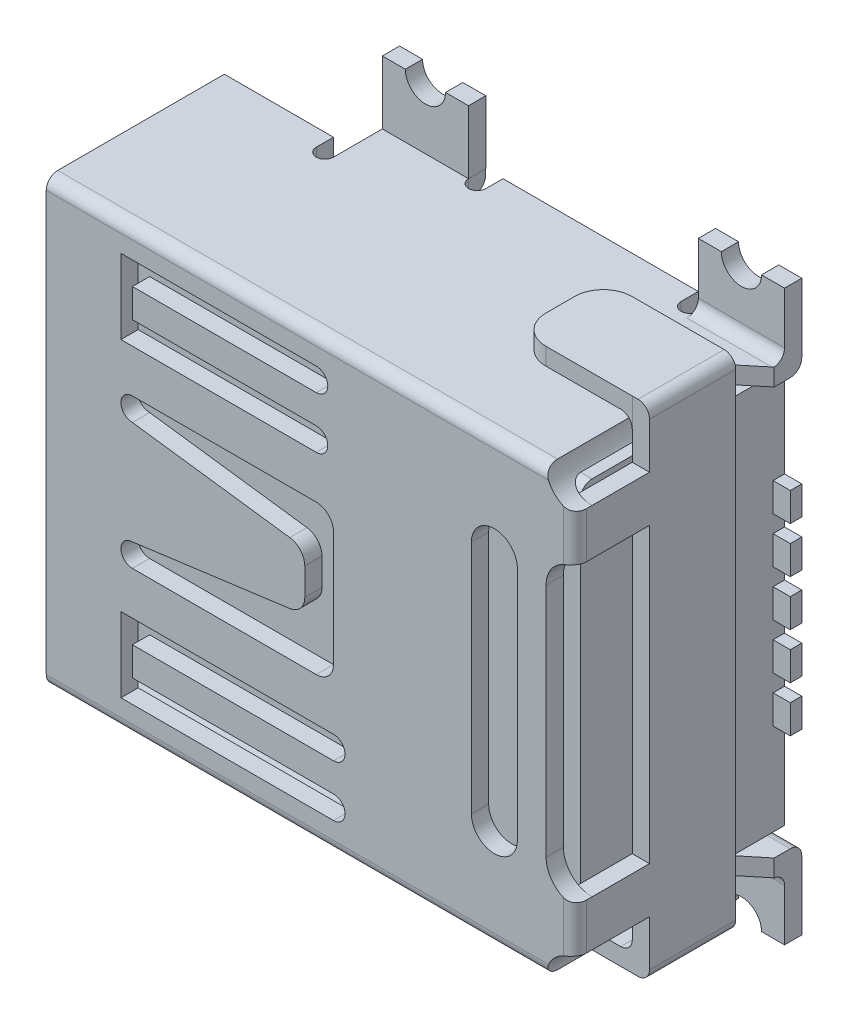
SolidWorks part; units mm, degrees
ref_plane "Front Plane" through (0, 0, 0) normal (0, 0, 1) x (1, 0, 0)
ref_plane "Top Plane" through (0, 0, 0) normal (0, 1, 0) x (1, 0, 0)
ref_plane "Right Plane" through (0, 0, 0) normal (1, 0, 0) x (0, 0, -1)
sketch "Sketch1" plane through (0, 0, 0) normal (0, 0, 1) x (1, 0, 0)
  line L0 (0, 0) -> (8.7, 0)
  line L1 (0, 7.7) -> (8.7, 7.7)
  line L2 (9.2, 7.2) -> (9.2, 6.4)
  line L3 (0, 7.7) -> (0, 0)
  line L4 (9.2, 0.5) -> (9.2, 1.3)
  line L5 (8.7, 5.9) -> (8.7, 1.8)
  line L6 (8.2, 1.8) -> (8.2, 5.9)
  line L7 (7.4, 5.9) -> (7.4, 1.8)
  line L9 (5, 4.85) -> (5, 2.85)
  line L10 (4.7, 5.15) -> (1.5, 5.15)
  line L11 (4.5, 4.0873) -> (4.5, 3.6127)
  line L12 (1.5, 4.75) -> (4.2396, 4.3847)
  line L13 (4.7, 2.55) -> (1.5, 2.55)
  line L14 (1.5, 2.95) -> (4.2396, 3.3153)
  line L15 (1.3, 5.9) -> (4.7, 5.9)
  line L16 (5, 1.8) -> (1.3, 1.8)
  line L17 (1.3, 5.9) -> (1.3, 7.2)
  line L18 (1.3, 1.8) -> (1.3, 0.5)
  line L19 (1.3, 7.2) -> (4.7, 7.2)
  line L20 (1.3, 0.5) -> (5, 0.5)
  line L21 (4.7, 6.8) -> (1.5, 6.8)
  line L22 (1.5, 6.8) -> (1.5, 6.3)
  line L23 (1.5, 6.3) -> (4.7, 6.3)
  line L24 (5, 1.4) -> (1.5, 1.4)
  line L25 (1.5, 1.4) -> (1.5, 0.9)
  line L26 (1.5, 0.9) -> (5, 0.9)
  arc A0 (8.7, 7.7) -> (9.2, 7.2) centre (9.2, 7.7) ccw
  arc A1 (8.7, 0) -> (9.2, 0.5) centre (9.2, 0) cw
  arc A2 (9.2, 6.4) -> (8.7, 5.9) centre (9.2, 5.9) ccw
  arc A3 (9.2, 1.3) -> (8.7, 1.8) centre (9.2, 1.8) cw
  arc A4 (8.2, 5.9) -> (7.4, 5.9) centre (7.8, 5.9) ccw
  arc A5 (7.4, 1.8) -> (8.2, 1.8) centre (7.8, 1.8) ccw
  arc A6 (1.5, 5.15) -> (1.5, 4.75) centre (1.5, 4.95) ccw
  arc A7 (4.7, 5.15) -> (5, 4.85) centre (4.7, 4.85) cw
  arc A8 (4.2396, 4.3847) -> (4.5, 4.0873) centre (4.2, 4.0873) cw
  arc A9 (1.5, 2.55) -> (1.5, 2.95) centre (1.5, 2.75) cw
  arc A10 (4.5, 3.6127) -> (4.2396, 3.3153) centre (4.2, 3.6127) cw
  arc A11 (5, 2.85) -> (4.7, 2.55) centre (4.7, 2.85) cw
  arc A12 (4.7, 7.2) -> (4.7, 6.8) centre (4.7, 7) cw
  arc A13 (4.7, 5.9) -> (4.7, 6.3) centre (4.7, 6.1) ccw
  arc A14 (5, 1.8) -> (5, 1.4) centre (5, 1.6) cw
  arc A15 (5, 0.5) -> (5, 0.9) centre (5, 0.7) ccw
  point P32 (5, 5.15)
  point P35 (4.5, 4.35)
  point P43 (5, 2.55)
  dimension "D1" = 9.2
  dimension "D2" = 7.7
extrude "Extrude1" add sketch "Sketch1" along normal blind 3.95
fillet "Fillet1" radius 0.2 1 edges at (4.35, 7.7, 3.95)
fillet "Fillet2" radius 0.2 1 edges at (4.35, 0, 3.95)
sketch "Sketch2" plane through (0, 0, 0) normal (-1, 0, 0) x (0, 0, 1)
  line L0 (0, 7.4) -> (3.65, 7.4)
  line L1 (0, 7.7) -> (0, 0) construction
  line L3 (3.65, 7.4) -> (3.65, 0.3)
  line L5 (3.65, 0.3) -> (0, 0.3)
  line L6 (0, 0.3) -> (0, 7.4)
extrude "Cut-Extrude1" cut sketch "Sketch2" against normal blind 9.2
fillet "Fillet5" radius 0.2 1 edges at (4.4, 7.4, 3.65)
fillet "Fillet9" radius 0.2 1 edges at (4.4, 0.3, 3.65)
sketch "Sketch4" plane through (0, 0, 0) normal (0, -1, 0) x (1, 0, 0)
  line L1 (0, 0) -> (8.7, 0) construction
  line L3 (2.2, 0.3) -> (2.2, 0)
  line L4 (3.7, 0.3) -> (3.7, 0)
  line L5 (2.2, 0.3) -> (3.7, 0.3)
  line L6 (3.7, 0) -> (2.2, 0)
extrude "Extrude3" add sketch "Sketch4" along normal blind 1.1
fillet "Fillet10" radius 0.2 1 edges at (2.95, 0, 0.3)
sketch "Sketch5" plane through (0, 0, 0) normal (0, -1, 0) x (1, 0, 0)
  line L0 (0, 0) -> (0, 0.85)
  line L1 (0, 3.75) -> (0, 0) construction
  line L3 (0, 0.85) -> (1.9, 0.85)
  line L4 (1.9, 0.85) -> (1.9, 1.35)
  line L5 (2.2, 0) -> (2.2, 1.35)
  line L6 (0, 0) -> (2.2, 0)
  arc A0 (1.9, 1.35) -> (2.2, 1.35) centre (2.05, 1.35) cw
extrude "Cut-Extrude2" cut sketch "Sketch5" against normal blind 0.3
sketch "Sketch6" plane through (0, 7.7, 0) normal (0, 1, 0) x (-1, 0, 0)
  line L0 (-2.2, 0.3) -> (-2.2, 0)
  line L3 (-8.7, 0) -> (0, 0) construction
  line L4 (-2.2, 0) -> (-3.7, 0)
  line L5 (-2.2, 0.3) -> (-3.7, 0.3)
  line L6 (-3.7, 0) -> (-3.7, 0.3)
extrude "Extrude4" add sketch "Sketch6" along normal blind 1.1
sketch "Sketch8" plane through (0, 7.7, 0) normal (0, 1, 0) x (-1, 0, 0)
  line L0 (0, 0) -> (0, 0.875)
  line L1 (0, 3.75) -> (0, 0) construction
  line L2 (0, 0.875) -> (-1.9, 0.875)
  line L3 (-2.2, 0.3) -> (-2.2, 1.15)
  line L4 (-1.9, 0.875) -> (-1.9, 1.15)
  line L5 (-2.2, 0.3) -> (-2.2, 0)
  line L6 (-2.2, 0) -> (0, 0)
  arc A0 (-1.9, 1.15) -> (-2.2, 1.15) centre (-2.05, 1.15) ccw
extrude "Cut-Extrude4" cut sketch "Sketch8" against normal blind 0.3
sketch "Sketch9" plane through (0, 0, 0) normal (0, -1, 0) x (1, 0, 0)
  line L0 (3.7, 0) -> (3.7, 0.5)
  line L1 (4, 0.5) -> (4, 0)
  line L2 (3.7, 0) -> (8.7, 0) construction
  line L3 (4, 0) -> (3.7, 0)
  arc A0 (3.7, 0.5) -> (4, 0.5) centre (3.85, 0.5) cw
extrude "Cut-Extrude5" cut sketch "Sketch9" against normal blind 0.3
fillet "Fillet11" radius 0.2 1 edges at (2.95, 0.3, 0)
sketch "Sketch10" plane through (0, 7.7, 0) normal (0, 1, 0) x (-1, 0, 0)
  line L0 (-3.6968, 0) -> (-3.7, 0.3)
  line L1 (-4, 0.2968) -> (-4, 0)
  line L2 (-8.7, 0) -> (-3.7, 0) construction
  line L3 (-4, 0) -> (-3.6968, 0)
  arc A0 (-3.7, 0.3) -> (-4, 0.2968) centre (-3.85, 0.2984) ccw
extrude "Cut-Extrude6" cut sketch "Sketch10" against normal blind 0.3
fillet "Fillet12" radius 0.2 1 edges at (2.9484, 7.4, 0)
sketch "Sketch11" plane through (9.2, 0, 0) normal (1, 0, 0) x (0, 0, -1)
  line L0 (-3.65, 7.2) -> (-2.65, 7.2)
  line L1 (-3.65, 6.4) -> (-2.65, 6.4)
  line L2 (-3.65, 7.2) -> (-3.65, 6.4)
  line L3 (-2.65, 7.2) -> (-2.65, 6.4)
extrude "Extrude5" add sketch "Sketch11" against normal blind 0.3
fillet "Fillet13" radius 0.2 1 edges at (9.2, 6.8, 3.95)
sketch "Sketch12" plane through (9.2, 0, 0) normal (1, 0, 0) x (0, 0, -1)
  line L0 (-3.65, 1.3) -> (-2.65, 1.3)
  line L1 (-3.65, 0.5) -> (-3.65, 1.3) construction
  line L2 (-3.65, 0.5) -> (-2.65, 0.5)
  line L3 (-3.65, 1.3) -> (-3.65, 0.5)
  line L4 (-2.65, 0.5) -> (-2.65, 1.3)
extrude "Extrude6" add sketch "Sketch12" against normal blind 0.3
fillet "Fillet14" radius 0.2 1 edges at (9.2, 0.9, 3.95)
sketch "Sketch13" plane through (0, 0, 2.65) normal (0, 0, -1) x (-1, 0, 0)
  line L0 (-9.2, 6.4) -> (-9.2, 1.3)
  line L1 (-8.9, 6.4) -> (-8.9, 0.5)
  line L2 (-8.9, 0.5) -> (-9.2, 0.5)
  line L3 (-9.2, 0.5) -> (-9.2, 1.3)
  line L4 (-8.9, 7.2) -> (-9.2, 7.2)
  line L5 (-9.2, 7.2) -> (-9.2, 6.4)
  line L6 (-8.9, 7.2) -> (-8.9, 6.4)
extrude "Extrude7" add sketch "Sketch13" along normal blind 1.5
sketch "Sketch14" plane through (0, 7.2, 0) normal (0, 1, 0) x (-1, 0, 0)
  line L0 (-9.2, 1.15) -> (-9.2, 2.65)
  line L1 (-9.2, 1.15) -> (-9.2, 3.65) construction
  line L2 (-9.2, 1.15) -> (-8.8974, 1.15)
  line L3 (-8.8974, 1.15) -> (-8.9, 2.65)
  line L4 (-8.9, 1.15) -> (-8.9, 3.65) construction
  line L5 (-8.9, 2.65) -> (-9.2, 2.65)
extrude "Extrude8" add sketch "Sketch14" along normal blind 1
sketch "Sketch15" plane through (0, 0.5, 0) normal (0, -1, 0) x (1, 0, 0)
  line L0 (9.2, 1.15) -> (9.2, 2.65)
  line L1 (9.2, 3.65) -> (9.2, 1.15) construction
  line L2 (9.2, 1.15) -> (8.9, 1.15)
  line L3 (8.9, 1.15) -> (8.9, 2.65)
  line L4 (8.9, 3.65) -> (8.9, 1.15) construction
  line L5 (8.9, 2.65) -> (9.2, 2.65)
extrude "Extrude9" add sketch "Sketch15" along normal blind 1
sketch "Sketch16" plane through (8.8954, 0, -0.0152) normal (-1, 0, 0.0017) x (0.0017, 0, 1)
  line L0 (2.6652, 8.2) -> (1.1652, 8.2)
  line L1 (1.1652, 8.2) -> (1.1652, 7.9)
  line L2 (1.1652, 8.2) -> (1.1652, 7.2) construction
  line L3 (1.1652, 7.9) -> (2.6652, 7.9)
  line L4 (2.6652, 8.2) -> (2.6652, 7.2) construction
  line L5 (2.6652, 8.2) -> (2.6652, 7.9)
extrude "Extrude10" add sketch "Sketch16" along normal blind 2
fillet "Fillet15" radius 0.2 1 edges at (9.2, 8.2, 1.9)
fillet "Fillet17" radius 0.2 1 edges at (8.8987, 7.9, 1.9)
sketch "Sketch17" plane through (8.9, 0, 0) normal (-1, 0, 0) x (0, 0, 1)
  line L0 (2.65, -0.5) -> (1.15, -0.5)
  line L1 (1.15, -0.5) -> (1.15, -0.2)
  line L2 (1.15, -0.5) -> (1.15, 7.2) construction
  line L3 (2.65, -0.5) -> (2.65, -0.2)
  line L4 (2.65, -0.5) -> (2.65, 0.5) construction
  line L5 (2.65, -0.2) -> (1.15, -0.2)
extrude "Extrude11" add sketch "Sketch17" along normal blind 2
fillet "Fillet18" radius 0.2 1 edges at (8.9, -0.2, 1.9)
fillet "Fillet19" radius 0.2 1 edges at (9.2, -0.5, 1.9)
fillet "Fillet20" radius 0.5 1 edges at (6.9, -0.35, 2.65)
fillet "Fillet21" radius 0.5 1 edges at (6.9, -0.35, 1.15)
fillet "Fillet22" radius 0.5 1 edges at (6.8974, 8.05, 1.1534)
fillet "Fillet23" radius 0.5 1 edges at (6.9, 8.05, 2.6534)
sketch "Sketch18" plane through (0, 0, 0.3) normal (0, 0, 1) x (1, 0, 0)
  line L2 (3.7, -1.1) -> (2.2, -1.1) construction
  line L4 (2.6, -1.1) -> (3.3, -1.1)
  arc A0 (3.3, -1.1) -> (2.6, -1.1) centre (2.95, -1.1) ccw
extrude "Cut-Extrude8" cut sketch "Sketch18" against normal blind 0.3
sketch "Sketch19" plane through (0, 0, 0.3) normal (0, 0, 1) x (1, 0, 0)
  line L0 (3.3, 8.8) -> (2.6, 8.8)
  line L1 (2.2, 8.8) -> (3.7, 8.8) construction
  arc A0 (2.6, 8.8) -> (3.3, 8.8) centre (2.95, 8.8) ccw
extrude "Cut-Extrude9" cut sketch "Sketch19" against normal blind 0.3
sketch "Sketch20" plane through (0, 0, 0) normal (0, -1, 0) x (1, 0, 0)
  line L0 (8.7, 0) -> (9.2, 0)
  line L1 (9.2, 0) -> (9.2, 0.4796)
  line L2 (9.2, 0.4796) -> (8.7, 0.8898)
  line L3 (8.7, 3.75) -> (8.7, 0) construction
  line L4 (8.7, 0.8898) -> (8.7, 0)
extrude "Extrude12" add sketch "Sketch20" against normal blind 0.3
sketch "Sketch21" plane through (0, 7.7, 0) normal (0, 1, 0) x (-1, 0, 0)
  line L0 (-8.7, 0) -> (-9.2, 0)
  line L1 (-9.2, 0) -> (-9.2, 0.4796)
  line L2 (-9.2, 0.4796) -> (-8.7, 0.8953)
  line L3 (-8.7, 3.75) -> (-8.7, 0) construction
  line L4 (-8.7, 0.8953) -> (-8.7, 0)
extrude "Extrude13" add sketch "Sketch21" against normal blind 0.3
sketch "Sketch22" plane through (0, 7.7, 0) normal (0, 1, 0) x (-1, 0, 0)
  line L0 (-9.2, 0) -> (-7.7, 0)
  line L1 (-9.2, 0) -> (-4, 0) construction
  line L3 (-9.2, 0) -> (-9.2, 0.3)
  line L4 (-9.2, 0.4796) -> (-9.2, 0) construction
  line L5 (-9.2, 0.3) -> (-7.7, 0.3)
  line L6 (-7.7, 0.3) -> (-7.7, 0)
extrude "Extrude14" add sketch "Sketch22" along normal blind 1.1
sketch "Sketch23" plane through (0, 7.7, 0) normal (0, 1, 0) x (-1, 0, 0)
  line L0 (-7.7, 0) -> (-7.7, 0.3)
  line L1 (-7.4, 0.3) -> (-7.4, 0)
  line L2 (-7.7, 0) -> (-4, 0) construction
  line L3 (-7.4, 0) -> (-7.7, 0)
  arc A0 (-7.7, 0.3) -> (-7.4, 0.3) centre (-7.55, 0.3) cw
extrude "Cut-Extrude10" cut sketch "Sketch23" against normal blind 0.3
fillet "Fillet24" radius 0.2 1 edges at (8.45, 7.7, 0.3)
fillet "Fillet25" radius 0.2 1 edges at (8.45, 7.4, 0)
sketch "Sketch24" plane through (0, 0, 0) normal (0, -1, 0) x (1, 0, 0)
  line L0 (9.2, 0) -> (9.2, 0.3)
  line L2 (9.2, 0) -> (9.2, 0.4796) construction
  line L3 (9.2, 0) -> (7.7, 0)
  line L4 (4, 0) -> (9.2, 0) construction
  line L5 (7.7, 0) -> (7.7, 0.3)
  line L6 (7.7, 0.3) -> (9.2, 0.3)
extrude "Extrude15" add sketch "Sketch24" along normal blind 1.1
sketch "Sketch25" plane through (0, 0, 0) normal (0, -1, 0) x (1, 0, 0)
  line L0 (7.7, 0) -> (7.7, 0.3)
  line L1 (7.4, 0.3) -> (7.4, 0)
  line L2 (4, 0) -> (7.7, 0) construction
  line L3 (7.4, 0) -> (7.7, 0)
  arc A0 (7.7, 0.3) -> (7.4, 0.3) centre (7.55, 0.3) ccw
extrude "Cut-Extrude11" cut sketch "Sketch25" against normal blind 0.3
sketch "Sketch26" plane through (0, 0, 0.3) normal (0, 0, 1) x (1, 0, 0)
  line L1 (9.2, -1.1) -> (7.7, -1.1) construction
  line L3 (8.1, -1.1) -> (8.8, -1.1)
  arc A0 (8.8, -1.1) -> (8.1, -1.1) centre (8.45, -1.1) ccw
extrude "Cut-Extrude12" cut sketch "Sketch26" against normal blind 0.3
fillet "Fillet26" radius 0.2 1 edges at (8.45, 0, 0.3)
fillet "Fillet27" radius 0.2 1 edges at (8.45, 0.3, 0)
sketch "Sketch27" plane through (0, 0, 0.3) normal (0, 0, 1) x (1, 0, 0)
  line L1 (7.7, 8.8) -> (9.2, 8.8) construction
  line L3 (8.8, 8.8) -> (8.1, 8.8)
  arc A0 (8.1, 8.8) -> (8.8, 8.8) centre (8.45, 8.8) ccw
extrude "Cut-Extrude13" cut sketch "Sketch27" against normal blind 0.3
sketch "Sketch29" plane through (0, 7.7, 0) normal (0, 1, 0) x (-1, 0, 0)
  line L0 (0, 0.875) -> (0, 0.85)
  line L1 (0, 0.875) -> (-1.9, 0.875)
  line L2 (-1.9, 0.875) -> (-1.9, 0.85)
  line L3 (-1.9, 0.85) -> (0, 0.85)
extrude "Extrude16" add sketch "Sketch29" against normal blind 0.3
sketch "Sketch30" plane through (0, 0, 0) normal (-1, 0, 0) x (0, 0, 1)
  line L0 (0.85, 7.1) -> (0.85, 6.3828)
  line L1 (1.05, 7.3) -> (3.35, 7.3)
  line L2 (3.45, 7.4) -> (0.85, 7.4) construction
  line L3 (3.55, 7.1) -> (3.55, 0.6)
  line L4 (3.35, 0.4) -> (1.05, 0.4)
  line L6 (0.85, 0.3) -> (3.45, 0.3) construction
  line L7 (0.85, 0.6) -> (0.85, 1.3172)
  line L8 (0.7914, 6.2414) -> (0.0586, 5.5086)
  line L9 (0.7914, 1.4586) -> (0.0586, 2.1914)
  line L10 (0, 2.3328) -> (0, 5.3672)
  arc A0 (3.35, 7.3) -> (3.55, 7.1) centre (3.35, 7.1) cw
  arc A1 (3.55, 0.6) -> (3.35, 0.4) centre (3.35, 0.6) cw
  arc A2 (0, 2.3328) -> (0.0586, 2.1914) centre (0.2, 2.3328) ccw
  arc A3 (0.7914, 1.4586) -> (0.85, 1.3172) centre (0.65, 1.3172) cw
  arc A4 (1.05, 0.4) -> (0.85, 0.6) centre (1.05, 0.6) cw
  arc A5 (0, 5.3672) -> (0.0586, 5.5086) centre (0.2, 5.3672) cw
  arc A6 (0.7914, 6.2414) -> (0.85, 6.3828) centre (0.65, 6.3828) ccw
  arc A7 (1.05, 7.3) -> (0.85, 7.1) centre (1.05, 7.1) ccw
  point P16 (3.55, 7.3)
  point P26 (0.85, 0.4)
  point P31 (0.85, 6.3)
  point P34 (0.85, 7.3)
  dimension "D2" = 0.2
  dimension "D1" = 0.1
  dimension "D3" = 0.1
extrude "Extrude17" add sketch "Sketch30" against normal blind 8.9
sketch "Sketch31" plane through (0, 0, 0) normal (0, 0, -1) x (-1, 0, 0)
  circle A0 centre (-5.9, 6.05) radius 0.3464
  circle A1 centre (-5.9, 1.65) radius 0.3464
extrude "Extrude18" add sketch "Sketch31" along normal blind 1 and the other way blind 1
sketch "Sketch33" plane through (0, 0, 0) normal (-1, 0, 0) x (0, 0, 1)
  line L0 (1.15, 7.2) -> (3.25, 7.2)
  line L1 (3.45, 7) -> (3.45, 0.7)
  line L2 (1.15, 0.5) -> (3.25, 0.5)
  line L3 (1.521, 2.18) -> (1.521, 2.58)
  line L4 (2.821, 5.85) -> (1.521, 5.85)
  line L5 (2.821, 1.85) -> (1.521, 1.85)
  line L6 (0.95, 0.7) -> (0.95, 1.3586)
  line L7 (0.95, 5.3) -> (0.95, 2.4)
  line L8 (0.95, 7) -> (0.95, 6.3414)
  line L9 (1.521, 2.58) -> (2.821, 2.58)
  line L10 (0.1586, 2.2328) -> (0.8914, 1.5)
  line L11 (2.821, 2.58) -> (2.821, 2.93)
  line L12 (0.1586, 5.4672) -> (0.8914, 6.2)
  line L13 (0.95, 5.3) -> (1.521, 5.85)
  line L14 (0.1, 5.3257) -> (0.1, 2.3743)
  line L15 (0.95, 2.4) -> (1.521, 1.85)
  line L16 (2.821, 5.52) -> (1.521, 5.52)
  line L17 (1.521, 5.52) -> (1.521, 5.12)
  line L18 (1.521, 5.12) -> (2.821, 5.12)
  line L19 (2.821, 3.33) -> (2.821, 3.66)
  line L20 (2.821, 4.79) -> (1.521, 4.79)
  line L21 (1.521, 4.79) -> (1.521, 4.39)
  line L22 (1.521, 4.39) -> (2.821, 4.39)
  line L23 (1.521, 2.18) -> (2.821, 2.18)
  line L24 (2.821, 4.06) -> (1.521, 4.06)
  line L25 (1.521, 4.06) -> (1.521, 3.66)
  line L26 (1.521, 3.66) -> (2.821, 3.66)
  line L27 (2.821, 4.06) -> (2.821, 4.39)
  line L28 (2.821, 3.33) -> (1.521, 3.33)
  line L29 (1.521, 3.33) -> (1.521, 2.93)
  line L30 (1.521, 2.93) -> (2.821, 2.93)
  line L31 (2.821, 4.79) -> (2.821, 5.12)
  line L32 (2.821, 5.52) -> (2.821, 5.85)
  line L33 (2.821, 1.85) -> (2.821, 2.18)
  arc A0 (3.45, 7) -> (3.25, 7.2) centre (3.25, 7) ccw
  arc A1 (1.15, 7.2) -> (0.95, 7) centre (1.15, 7) ccw
  arc A2 (3.45, 0.7) -> (3.25, 0.5) centre (3.25, 0.7) cw
  arc A3 (0.95, 0.7) -> (1.15, 0.5) centre (1.15, 0.7) ccw
  arc A4 (0.8914, 1.5) -> (0.95, 1.3586) centre (0.75, 1.3586) cw
  arc A5 (0.1, 2.3743) -> (0.1586, 2.2328) centre (0.3, 2.3743) ccw
  arc A6 (0.8914, 6.2) -> (0.95, 6.3414) centre (0.75, 6.3414) ccw
  arc A7 (0.1586, 5.4672) -> (0.1, 5.3257) centre (0.3, 5.3257) ccw
extrude "Cut-Extrude14" cut sketch "Sketch33" against normal blind 2.5
sketch "Sketch34" plane through (0, 0, 0) normal (-1, 0, 0) x (0, 0, 1)
  line L0 (2.821, 5.85) -> (2.821, 5.52)
  line L1 (2.821, 5.52) -> (1.521, 5.52)
  line L2 (1.521, 5.52) -> (1.521, 5.12)
  line L3 (1.521, 5.12) -> (2.821, 5.12)
  line L4 (2.821, 5.12) -> (2.821, 4.79)
  line L5 (2.821, 4.79) -> (1.521, 4.79)
  line L6 (1.521, 4.79) -> (1.521, 4.39)
  line L7 (1.521, 4.39) -> (2.821, 4.39)
  line L8 (2.821, 4.39) -> (2.821, 4.06)
  line L9 (2.821, 4.06) -> (1.521, 4.06)
  line L10 (1.521, 4.06) -> (1.521, 3.66)
  line L11 (1.521, 3.66) -> (2.821, 3.66)
  line L12 (2.821, 3.66) -> (2.821, 3.33)
  line L13 (2.821, 3.33) -> (1.521, 3.33)
  line L14 (1.521, 3.33) -> (1.521, 2.93)
  line L15 (1.521, 2.93) -> (2.821, 2.93)
  line L16 (2.821, 2.93) -> (2.821, 2.58)
  line L17 (2.821, 2.58) -> (1.521, 2.58)
  line L18 (1.521, 2.58) -> (1.521, 2.18)
  line L19 (1.521, 2.18) -> (2.821, 2.18)
  line L20 (2.821, 2.18) -> (2.821, 1.85)
  line L21 (2.821, 1.85) -> (1.521, 1.85)
  line L22 (1.521, 1.85) -> (0.95, 2.4)
  line L23 (0.95, 2.4) -> (0.95, 5.3)
  line L24 (0.95, 5.3) -> (1.521, 5.85)
  line L25 (1.521, 5.85) -> (2.821, 5.85)
extrude "Cut-Extrude15" cut sketch "Sketch34" against normal blind 1
sketch "Sketch35" plane through (2.5, 0, 0) normal (-1, 0, 0) x (0, 0, 1)
  line L0 (1.521, 5.52) -> (2.971, 5.52)
  line L2 (1.521, 5.52) -> (1.521, 5.12)
  line L3 (1.521, 5.12) -> (2.821, 5.12)
  line L4 (2.821, 5.12) -> (2.971, 5.12)
  line L5 (2.971, 5.12) -> (2.971, 5.52)
  line L6 (1.521, 3.66) -> (2.971, 3.66)
  line L7 (1.521, 4.39) -> (2.971, 4.39)
  line L8 (1.521, 2.93) -> (2.971, 2.93)
  line L9 (1.521, 2.18) -> (2.971, 2.18)
  line L10 (1.521, 2.18) -> (1.521, 2.58)
  line L11 (1.521, 2.58) -> (2.971, 2.58)
  line L12 (2.971, 2.58) -> (2.971, 2.18)
  line L13 (1.521, 2.93) -> (1.521, 3.33)
  line L14 (1.521, 3.33) -> (2.971, 3.33)
  line L15 (2.971, 3.33) -> (2.971, 2.93)
  line L16 (1.521, 3.66) -> (1.521, 4.06)
  line L17 (1.521, 4.06) -> (2.971, 4.06)
  line L18 (2.971, 4.06) -> (2.971, 3.66)
  line L19 (1.521, 4.39) -> (1.521, 4.79)
  line L20 (1.521, 4.79) -> (2.971, 4.79)
  line L21 (2.971, 4.79) -> (2.971, 4.39)
extrude "Extrude19" add sketch "Sketch35" along normal blind 2
sketch "Sketch36" plane through (8.9, 0, 0) normal (1, 0, 0) x (0, 0, -1)
  line L0 (-1.05, 7.3) -> (0, 7.3)
  line L1 (0, 7.3) -> (0, 0.4)
  line L2 (0, 0.4) -> (-1.05, 0.4)
  line L3 (-1.05, 0.4) -> (-1.05, 7.3)
extrude "Extrude20" add sketch "Sketch36" against normal blind 7
sketch "Sketch37" plane through (8.9, 0, 0) normal (1, 0, 0) x (0, 0, -1)
  line L0 (0, 4.9) -> (-0.2, 4.9)
  line L1 (0, 7.3) -> (0, 0.4) construction
  line L2 (-0.2, 4.9) -> (-0.2, 4.4)
  line L3 (-0.2, 4.4) -> (0, 4.4)
  line L4 (0, 4.4) -> (0, 4.9)
  line L5 (0, 4.1) -> (-0.2, 4.1)
  line L6 (-0.2, 4.1) -> (-0.2, 3.6)
  line L7 (-0.2, 3.6) -> (0, 3.6)
  line L8 (0, 5.2) -> (-0.2, 5.2)
  line L9 (-0.2, 5.2) -> (-0.2, 5.7)
  line L10 (-0.2, 5.7) -> (0, 5.7)
  line L11 (0, 5.7) -> (0, 5.2)
  line L12 (0, 3.6) -> (0, 4.1)
  line L13 (0, 3.3) -> (-0.2, 3.3)
  line L14 (-0.2, 3.3) -> (-0.2, 2.8)
  line L15 (-0.2, 2.8) -> (0, 2.8)
  line L16 (0, 2.8) -> (0, 3.3)
  line L17 (0, 2.5) -> (-0.2, 2.5)
  line L18 (-0.2, 2.5) -> (-0.2, 2)
  line L19 (-0.2, 2) -> (0, 2)
  line L20 (0, 2) -> (0, 2.5)
extrude "Cut-Extrude16" cut sketch "Sketch37" against normal blind 2
sketch "Sketch38" plane through (0, 0, 0.2) normal (0, 0, -1) x (-1, 0, 0)
  line L0 (-6.9, 5.7) -> (-9.2, 5.7)
  line L1 (-9.2, 8) -> (-9.2, -0.3) construction
  line L2 (-6.9, 5.7) -> (-6.9, 5.2)
  line L3 (-6.9, 5.2) -> (-9.2, 5.2)
  line L4 (-9.2, 5.2) -> (-9.2, 5.7)
  line L5 (-6.9, 4.9) -> (-6.9, 4.4)
  line L6 (-6.9, 4.4) -> (-9.2, 4.4)
  line L7 (-9.2, 4.4) -> (-9.2, 4.9)
  line L8 (-9.2, 4.9) -> (-6.9, 4.9)
  line L9 (-6.9, 4.1) -> (-6.9, 3.6)
  line L10 (-6.9, 3.6) -> (-9.2, 3.6)
  line L11 (-9.2, 3.6) -> (-9.2, 4.1)
  line L12 (-9.2, 4.1) -> (-6.9, 4.1)
  line L13 (-6.9, 3.3) -> (-6.9, 2.8)
  line L14 (-6.9, 2.8) -> (-9.2, 2.8)
  line L15 (-9.2, 2.8) -> (-9.2, 3.3)
  line L16 (-9.2, 3.3) -> (-6.9, 3.3)
  line L17 (-6.9, 2.5) -> (-6.9, 2)
  line L18 (-6.9, 2) -> (-9.2, 2)
  line L19 (-9.2, 2) -> (-9.2, 2.5)
  line L20 (-9.2, 2.5) -> (-6.9, 2.5)
extrude "Extrude21" add sketch "Sketch38" along normal blind 0.2
